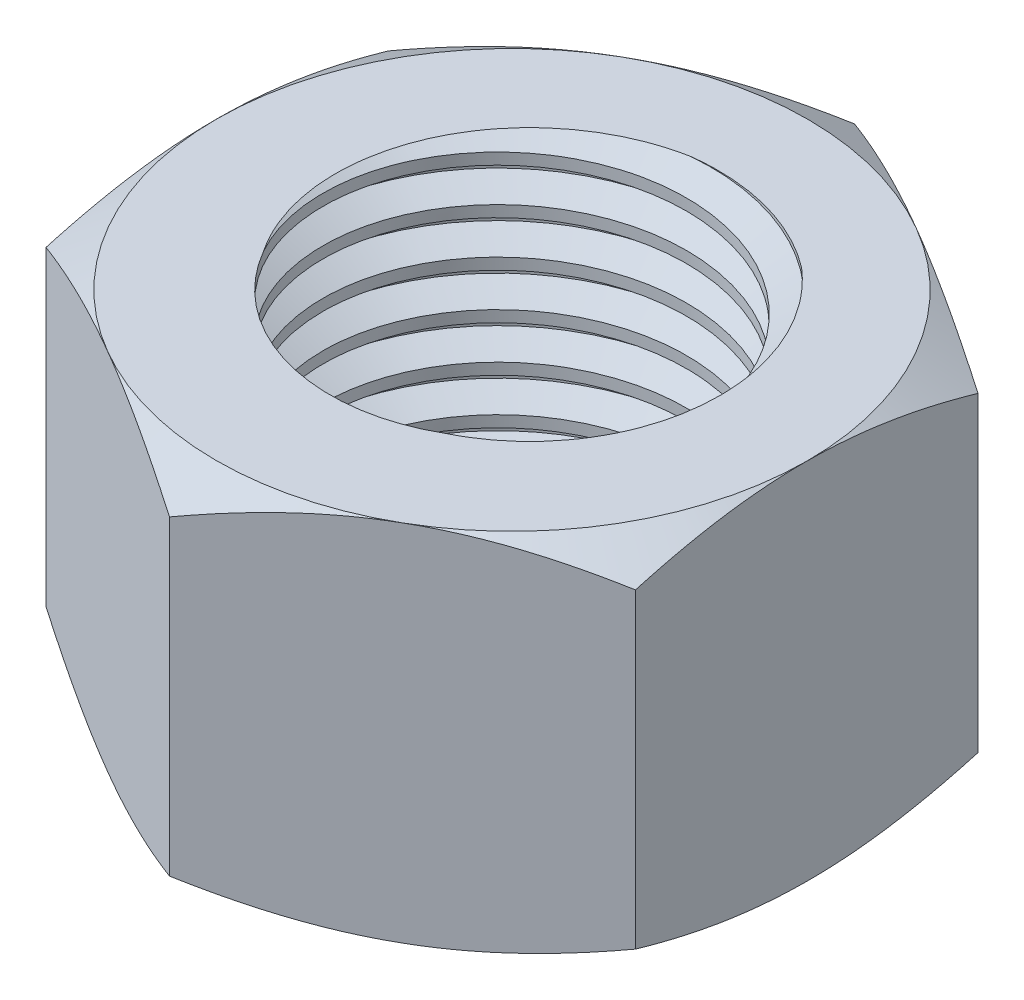
SolidWorks part; units mm, degrees
ref_plane "Front Plane" through (0, 0, 0) normal (0, 0, 1) x (1, 0, 0)
ref_plane "Top Plane" through (0, 0, 0) normal (0, 1, 0) x (1, 0, 0)
ref_plane "Right Plane" through (0, 0, 0) normal (1, 0, 0) x (0, 0, -1)
sketch "Sketch1" plane through (0, 0, 0) normal (0, 1, 0) x (1, 0, 0)
  line L1 (-19.5359, -11.196) -> (-0.0719, -22.5165)
  line L2 (-0.0719, -22.5165) -> (19.4639, -11.3206)
  line L3 (19.4639, -11.3206) -> (19.5359, 11.196)
  line L4 (19.5359, 11.196) -> (0.0719, 22.5165)
  line L5 (0.0719, 22.5165) -> (-19.4639, 11.3206)
  line L6 (-19.4639, 11.3206) -> (-19.5359, -11.196)
  circle A0 centre (0, 0) radius 19.5 construction
  circle A1 centre (0, 0) radius 12
  dimension "D1" = 39
  dimension "D2" = 24
extrude "Boss-Extrude1" add sketch "Sketch1" along normal blind 24
sketch "Sketch2" plane through (0, 24, 0) normal (0, 1, 0) x (1, 0, 0)
  circle A0 centre (0, 0) radius 19.5
extrude "Cut-Extrude1" cut sketch "Sketch2" against normal blind 24 draft 60 flip side to cut
sketch "Sketch4" plane through (0, 0, 0) normal (0, -1, 0) x (1, 0, 0)
  circle A0 centre (0, 0) radius 19.5
extrude "Cut-Extrude2" cut sketch "Sketch4" against normal blind 24 draft 60 flip side to cut
ref_axis "Axis1" through (0, 24, 0) along (0, -1, 0)
thread "Thread1" pitch 3 method cut trim with start face yes trim with end face yes profile "Thread Profile4" start angle 0, offset 5, length 30, pitch 3, diameter 24
ref_plane "Plane4" through (-12, 29, 0) normal (0, 0, 1) x (-1, 0, 0)
sketch "Thread Profile4" plane through (-12, 29, 0) normal (0, 0, 1) x (-1, 0, 0)
  line L0 (0, 0) -> (0, 3) construction
  line L1 (0, 0) -> (1.6238, 0.9375)
  line L2 (1.6238, 0.9375) -> (1.6238, 1.3125)
  line L3 (1.6238, 1.3125) -> (0, 2.25)
  line L4 (1.6238, 1.125) -> (0, 1.125) construction
  line L11 (0, 0) -> (0, 2.25)
  point P2 (0, 0)
  dimension "Pitch" = 3
  dimension "Profile_Angle" = 60
  dimension "Profile_Land" = 0.375
  dimension "Profile_Height" = 1.6238
